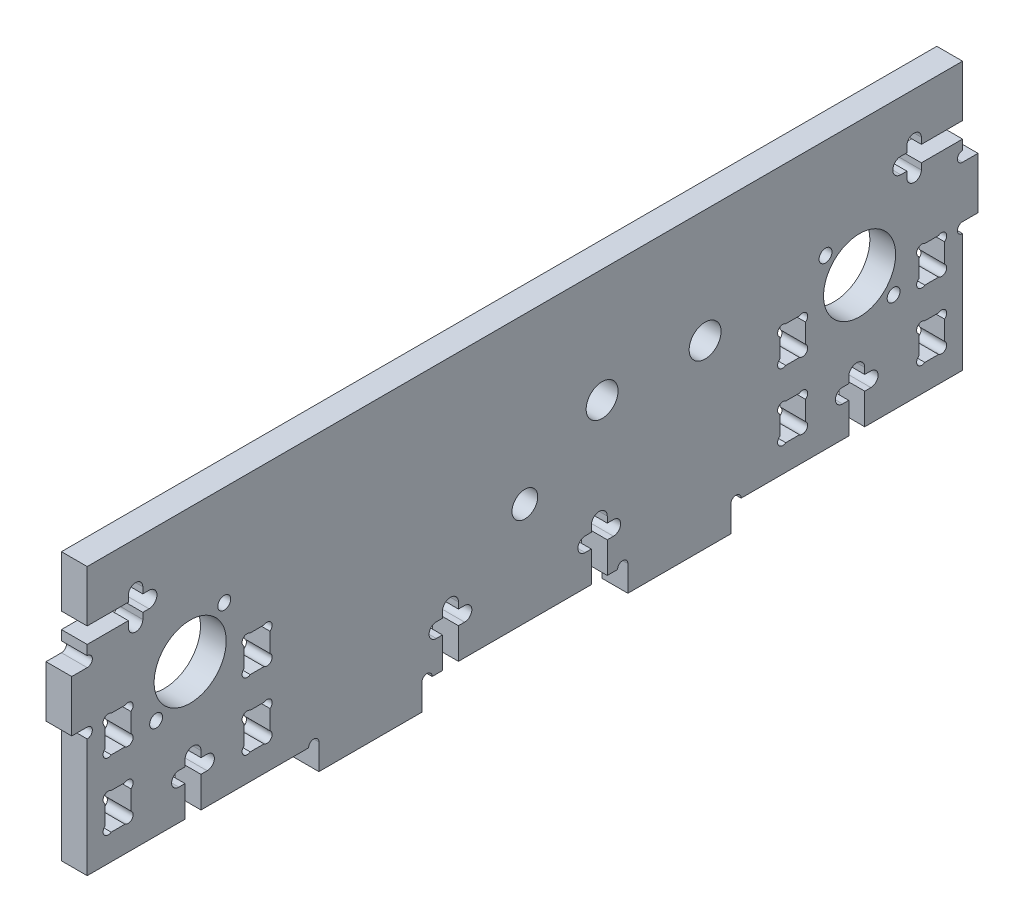
SolidWorks part; units mm, degrees
ref_plane "정면" through (0, 0, 0) normal (0, 0, 1) x (1, 0, 0)
ref_plane "윗면" through (0, 0, 0) normal (0, 1, 0) x (1, 0, 0)
ref_plane "우측면" through (0, 0, 0) normal (1, 0, 0) x (0, 0, -1)
sketch "스케치1" plane through (0, 0, 0) normal (1, 0, 0) x (0, 0, -1)
  line L1 (0, 0) -> (170, 0)
  line L2 (0, 0) -> (0, 52)
  line L3 (0, 52) -> (170, 52)
  line L4 (170, 0) -> (170, 52)
  dimension "D1" = 170
  dimension "D2" = 52
extrude "보스-돌출1" add sketch "스케치1" along normal blind 5
sketch "스케치2" plane through (5, 0, 0) normal (1, 0, 0) x (0, 0, -1)
  line L0 (170, 26) -> (150, 26) construction
  line L1 (170, 0) -> (170, 52) construction
  line L2 (150, 26) -> (20, 26) construction
  line L3 (20, 26) -> (0, 26) construction
  line L4 (0, 52) -> (0, 0) construction
  circle A0 centre (150, 26) radius 7
  circle A1 centre (20, 26) radius 7
  dimension "D2" = 14
  dimension "D1" = 20
extrude "컷-돌출1" cut sketch "스케치2" against normal blind 10
sketch "스케치3" plane through (5, 0, 0) normal (1, 0, 0) x (0, 0, -1)
  line L0 (0, 0) -> (170, 0) construction
  line L1 (45, 0) -> (65, 0)
  line L2 (45, 0) -> (45, -5)
  line L3 (45, -5) -> (65, -5)
  line L4 (65, 0) -> (65, -5)
  line L5 (0, -5) -> (45, -5) construction
  line L6 (65, -5) -> (105, -5) construction
  line L7 (125, 0) -> (105, 0)
  line L8 (125, 0) -> (125, -5)
  line L9 (125, -5) -> (105, -5)
  line L10 (105, 0) -> (105, -5)
  line L11 (125, -5) -> (170, -5) construction
  line L12 (170, -5) -> (170, 0) construction
  line L13 (0, 0) -> (0, -5) construction
  line L14 (0, 0) -> (0, -5) construction
  line L15 (0, -5) -> (45, -5) construction
  dimension "D1" = 45
  dimension "D2" = 20
extrude "보스-돌출2" add sketch "스케치3" against normal blind 5
sketch "스케치6" plane through (5, 0, 0) normal (1, 0, 0) x (0, 0, -1)
  line L0 (151, 0) -> (151, 6)
  line L1 (147.9, 10) -> (151, 10) construction
  line L2 (146.7, 6) -> (146.7, 8.8) construction
  line L3 (151, 6) -> (151, 8.8) construction
  line L4 (147.9, 0) -> (151, 0)
  line L5 (146.7, 8.8) -> (147.9, 8.8)
  line L6 (147.9, 0) -> (147.9, 6)
  line L7 (152.2, 8.8) -> (152.2, 6) construction
  line L8 (147.9, 6) -> (146.7, 6)
  line L9 (147.9, 8.8) -> (147.9, 6) construction
  line L10 (151, 8.8) -> (151, 10)
  line L11 (147.9, 6) -> (151, 6) construction
  line L12 (147.9, 8.8) -> (151, 8.8) construction
  line L13 (151, 8.8) -> (152.2, 8.8)
  line L14 (147.9, 8.8) -> (147.9, 10)
  line L15 (149.45, 10) -> (149.45, 12.1831) construction
  line L16 (152.2, 6) -> (151, 6)
  line L18 (65, 0) -> (105, 0) construction
  line L19 (101, 0) -> (101, 6)
  line L20 (97.9, 10) -> (101, 10) construction
  line L21 (96.7, 6) -> (96.7, 8.8) construction
  line L22 (101, 6) -> (101, 8.8) construction
  line L23 (97.9, 0) -> (101, 0)
  line L24 (96.7, 8.8) -> (97.9, 8.8)
  line L25 (97.9, 0) -> (97.9, 6)
  line L26 (102.2, 8.8) -> (102.2, 6) construction
  line L27 (97.9, 6) -> (96.7, 6)
  line L28 (97.9, 8.8) -> (97.9, 6) construction
  line L29 (101, 8.8) -> (101, 10)
  line L30 (97.9, 6) -> (101, 6) construction
  line L31 (97.9, 8.8) -> (101, 8.8) construction
  line L32 (101, 8.8) -> (102.2, 8.8)
  line L33 (97.9, 8.8) -> (97.9, 10)
  line L34 (99.45, 10) -> (99.45, 12.1831) construction
  line L35 (102.2, 6) -> (101, 6)
  line L37 (105, 0) -> (105, -5) construction
  line L71 (85, 52) -> (85, 0) construction
  line L72 (170, 52) -> (0, 52) construction
  line L89 (70.55, 10) -> (70.55, 12.1831) construction
  line L90 (72.1, 8.8) -> (69, 8.8) construction
  line L91 (72.1, 6) -> (69, 6) construction
  line L92 (72.1, 8.8) -> (72.1, 6) construction
  line L93 (67.8, 8.8) -> (67.8, 6) construction
  line L94 (69, 6) -> (69, 8.8) construction
  line L95 (73.3, 6) -> (73.3, 8.8) construction
  line L96 (72.1, 10) -> (69, 10) construction
  line L97 (20.55, 10) -> (20.55, 12.1831) construction
  line L98 (22.1, 8.8) -> (19, 8.8) construction
  line L99 (22.1, 6) -> (19, 6) construction
  line L100 (22.1, 8.8) -> (22.1, 6) construction
  line L101 (17.8, 8.8) -> (17.8, 6) construction
  line L102 (19, 6) -> (19, 8.8) construction
  line L103 (23.3, 6) -> (23.3, 8.8) construction
  line L104 (22.1, 10) -> (19, 10) construction
  line L123 (67.8, 6) -> (69, 6)
  line L124 (72.1, 8.8) -> (72.1, 10)
  line L125 (69, 8.8) -> (67.8, 8.8)
  line L126 (69, 8.8) -> (69, 10)
  line L127 (72.1, 6) -> (73.3, 6)
  line L128 (72.1, 0) -> (72.1, 6)
  line L129 (73.3, 8.8) -> (72.1, 8.8)
  line L130 (72.1, 0) -> (69, 0)
  line L131 (69, 0) -> (69, 6)
  line L132 (17.8, 6) -> (19, 6)
  line L133 (22.1, 8.8) -> (22.1, 10)
  line L134 (19, 8.8) -> (17.8, 8.8)
  line L135 (19, 8.8) -> (19, 10)
  line L136 (22.1, 6) -> (23.3, 6)
  line L137 (22.1, 0) -> (22.1, 6)
  line L138 (23.3, 8.8) -> (22.1, 8.8)
  line L139 (22.1, 0) -> (19, 0)
  line L140 (19, 0) -> (19, 6)
  arc A0 (151, 10) -> (147.9, 10) centre (149.45, 10) ccw
  arc A1 (146.7, 8.8) -> (146.7, 6) centre (146.7, 7.4) ccw
  arc A2 (152.2, 6) -> (152.2, 8.8) centre (152.2, 7.4) ccw
  arc A3 (101, 10) -> (97.9, 10) centre (99.45, 10) ccw
  arc A4 (96.7, 8.8) -> (96.7, 6) centre (96.7, 7.4) ccw
  arc A5 (102.2, 6) -> (102.2, 8.8) centre (102.2, 7.4) ccw
  arc A18 (67.8, 6) -> (67.8, 8.8) centre (67.8, 7.4) cw
  arc A19 (73.3, 8.8) -> (73.3, 6) centre (73.3, 7.4) cw
  arc A20 (69, 10) -> (72.1, 10) centre (70.55, 10) cw
  arc A21 (17.8, 6) -> (17.8, 8.8) centre (17.8, 7.4) cw
  arc A22 (23.3, 8.8) -> (23.3, 6) centre (23.3, 7.4) cw
  arc A23 (19, 10) -> (22.1, 10) centre (20.55, 10) cw
  dimension "D1" = 3.1
  dimension "D2" = 4
  dimension "D3" = 5.5
  dimension "D4" = 2.8
  dimension "D7" = 3.1
  dimension "D9" = 5.5
  dimension "D10" = 2.8
  dimension "D12" = 50
extrude "컷-돌출2" cut sketch "스케치6" against normal blind 10
sketch "스케치8" plane through (5, 0, 0) normal (1, 0, 0) x (0, 0, -1)
  line L0 (170, 0) -> (170, 52) construction
  line L1 (170, 35) -> (173, 35)
  line L2 (170, 35) -> (170, 25)
  line L3 (170, 25) -> (173, 25)
  line L4 (173, 35) -> (173, 25)
  line L5 (173, 52) -> (173, 35) construction
  line L8 (85, 0) -> (85, 52) construction
  line L9 (72.1, 0) -> (97.9, 0) construction
  line L10 (170, 52) -> (0, 52) construction
  line L11 (-3, 35) -> (-3, 25)
  line L12 (0, 25) -> (-3, 25)
  line L13 (0, 35) -> (0, 25)
  line L14 (0, 35) -> (-3, 35)
  line L15 (151, 0) -> (170, 0) construction
  dimension "D1" = 25
  dimension "D2" = 10
extrude "보스-돌출3" add sketch "스케치8" against normal blind 5
sketch "스케치7" plane through (5, 0, 0) normal (1, 0, 0) x (0, 0, -1)
  line L0 (65, 0) -> (69, 0) construction
  line L1 (22.1, 0) -> (45, 0) construction
  line L2 (101, 0) -> (105, 0) construction
  line L3 (125, 0) -> (147.9, 0) construction
  line L4 (170, 35) -> (170, 52) construction
  line L5 (170, 0) -> (170, 25) construction
  line L6 (0, 52) -> (0, 35) construction
  line L7 (0, 25) -> (0, 0) construction
  circle A0 centre (66, 0) radius 1
  circle A1 centre (44, 0) radius 1
  circle A2 centre (104, 0) radius 1
  circle A3 centre (126, 0) radius 1
  circle A4 centre (170, 36) radius 1
  circle A5 centre (170, 24) radius 1
  circle A6 centre (0, 36) radius 1
  circle A7 centre (0, 24) radius 1
  dimension "D1" = 2
extrude "컷-돌출3" cut sketch "스케치7" against normal blind 10
sketch "스케치10" plane through (0, 0, 0) normal (-1, 0, 0) x (0, 0, 1)
  line L0 (-166.5, 25) -> (-161.5, 18) construction
  line L1 (-166.5, 18) -> (-161.5, 18)
  line L2 (-166.5, 18) -> (-166.5, 25)
  line L3 (-166.5, 25) -> (-161.5, 25)
  line L4 (-161.5, 18) -> (-161.5, 25)
  line L5 (-161.5, 25) -> (-166.5, 18) construction
  line L6 (-85, 52) -> (-85, 0) construction
  line L7 (-139.5, 18) -> (-134.5, 18)
  line L8 (-139.5, 18) -> (-139.5, 25)
  line L9 (-139.5, 25) -> (-134.5, 25)
  line L10 (-134.5, 18) -> (-134.5, 25)
  line L11 (-166.5, 5) -> (-161.5, 5)
  line L12 (-166.5, 5) -> (-166.5, 12)
  line L13 (-166.5, 12) -> (-161.5, 12)
  line L14 (-161.5, 5) -> (-161.5, 12)
  line L15 (-139.5, 12) -> (-134.5, 12)
  line L16 (-139.5, 12) -> (-139.5, 5)
  line L17 (-139.5, 5) -> (-134.5, 5)
  line L18 (-134.5, 12) -> (-134.5, 5)
  line L19 (-170, 52) -> (0, 52) construction
  line L20 (-72.1, 0) -> (-97.9, 0) construction
  line L21 (-8.5, 25) -> (-3.5, 18) construction
  line L22 (-3.5, 25) -> (-8.5, 18) construction
  line L23 (-35.5, 12) -> (-35.5, 5)
  line L24 (-30.5, 5) -> (-35.5, 5)
  line L25 (-30.5, 12) -> (-30.5, 5)
  line L26 (-30.5, 12) -> (-35.5, 12)
  line L27 (-8.5, 5) -> (-8.5, 12)
  line L28 (-3.5, 12) -> (-8.5, 12)
  line L29 (-3.5, 5) -> (-3.5, 12)
  line L30 (-3.5, 5) -> (-8.5, 5)
  line L31 (-35.5, 18) -> (-35.5, 25)
  line L32 (-30.5, 25) -> (-35.5, 25)
  line L33 (-30.5, 18) -> (-30.5, 25)
  line L34 (-30.5, 18) -> (-35.5, 18)
  line L35 (-8.5, 18) -> (-8.5, 25)
  line L36 (-3.5, 25) -> (-8.5, 25)
  line L37 (-3.5, 18) -> (-3.5, 25)
  line L38 (-3.5, 18) -> (-8.5, 18)
extrude "컷-돌출4" cut sketch "스케치10" against normal blind 10
sketch "스케치11" plane through (5, 0, 0) normal (1, 0, 0) x (0, 0, -1)
  line L0 (85, 52) -> (85, 0) construction
  line L1 (170, 52) -> (0, 52) construction
  line L2 (72.1, 0) -> (97.9, 0) construction
  line L3 (161.5, 25) -> (166.5, 18) construction
  line L4 (166.5, 25) -> (161.5, 18) construction
  line L5 (139.5, 18) -> (161.5, 18) construction
  line L6 (161.5, 18) -> (161.5, 12) construction
  line L7 (161.5, 12) -> (139.5, 12) construction
  line L8 (139.5, 12) -> (139.5, 18) construction
  line L9 (150.5, 18) -> (150.5, 12) construction
  line L10 (139.5, 15) -> (161.5, 15) construction
  line L11 (134.5, 25) -> (139.5, 18) construction
  line L12 (139.5, 25) -> (134.5, 18) construction
  line L13 (139.5, 5) -> (134.5, 12) construction
  line L14 (134.5, 5) -> (139.5, 12) construction
  line L15 (166.5, 5) -> (161.5, 12) construction
  line L16 (161.5, 5) -> (166.5, 12) construction
  line L17 (8.5, 5) -> (3.5, 12) construction
  line L18 (3.5, 5) -> (8.5, 12) construction
  line L19 (35.5, 5) -> (30.5, 12) construction
  line L20 (30.5, 5) -> (35.5, 12) construction
  line L21 (30.5, 25) -> (35.5, 18) construction
  line L22 (35.5, 25) -> (30.5, 18) construction
  line L23 (30.5, 15) -> (8.5, 15) construction
  line L24 (19.5, 18) -> (19.5, 12) construction
  line L25 (30.5, 12) -> (30.5, 18) construction
  line L26 (8.5, 12) -> (30.5, 12) construction
  line L27 (8.5, 18) -> (8.5, 12) construction
  line L28 (30.5, 18) -> (8.5, 18) construction
  line L29 (3.5, 25) -> (8.5, 18) construction
  line L30 (8.5, 25) -> (3.5, 18) construction
  circle A0 centre (165.9188, 24.1863) radius 1
  circle A1 centre (162.0812, 24.1863) radius 1
  circle A2 centre (165.9188, 18.8137) radius 1
  circle A3 centre (162.0812, 18.8137) radius 1
  circle A4 centre (138.9188, 18.8137) radius 1
  circle A5 centre (135.0812, 18.8137) radius 1
  circle A6 centre (138.9188, 24.1863) radius 1
  circle A7 centre (135.0812, 24.1863) radius 1
  circle A8 centre (135.0812, 5.8137) radius 1
  circle A9 centre (138.9188, 5.8137) radius 1
  circle A10 centre (135.0812, 11.1863) radius 1
  circle A11 centre (138.9188, 11.1863) radius 1
  circle A12 centre (162.0812, 11.1863) radius 1
  circle A13 centre (165.9188, 11.1863) radius 1
  circle A14 centre (162.0812, 5.8137) radius 1
  circle A15 centre (165.9188, 5.8137) radius 1
  circle A16 centre (4.0812, 5.8137) radius 1
  circle A17 centre (7.9188, 5.8137) radius 1
  circle A18 centre (4.0812, 11.1863) radius 1
  circle A19 centre (7.9188, 11.1863) radius 1
  circle A20 centre (31.0812, 11.1863) radius 1
  circle A21 centre (34.9188, 11.1863) radius 1
  circle A22 centre (31.0812, 5.8137) radius 1
  circle A23 centre (34.9188, 5.8137) radius 1
  circle A24 centre (34.9188, 24.1863) radius 1
  circle A25 centre (31.0812, 24.1863) radius 1
  circle A26 centre (34.9188, 18.8137) radius 1
  circle A27 centre (31.0812, 18.8137) radius 1
  circle A28 centre (7.9188, 18.8137) radius 1
  circle A29 centre (4.0812, 18.8137) radius 1
  circle A30 centre (7.9188, 24.1863) radius 1
  circle A31 centre (4.0812, 24.1863) radius 1
  dimension "D1" = 2
extrude "컷-돌출5" cut sketch "스케치11" against normal blind 10
sketch "스케치12" plane through (5, 0, 0) normal (1, 0, 0) x (0, 0, -1)
  line L0 (170, 42) -> (162, 42)
  line L1 (158, 38.9) -> (158, 42) construction
  line L2 (162, 37.7) -> (159.2, 37.7) construction
  line L3 (162, 42) -> (159.2, 42) construction
  line L4 (170, 38.9) -> (170, 42)
  line L5 (159.2, 37.7) -> (159.2, 38.9)
  line L6 (170, 38.9) -> (162, 38.9)
  line L7 (159.2, 43.2) -> (162, 43.2) construction
  line L8 (162, 38.9) -> (162, 37.7)
  line L9 (159.2, 38.9) -> (162, 38.9) construction
  line L10 (159.2, 42) -> (158, 42)
  line L11 (162, 38.9) -> (162, 42) construction
  line L12 (159.2, 38.9) -> (159.2, 42) construction
  line L13 (159.2, 42) -> (159.2, 43.2)
  line L14 (159.2, 38.9) -> (158, 38.9)
  line L15 (158, 40.45) -> (156.45, 40.45) construction
  line L16 (162, 43.2) -> (162, 42)
  line L17 (160.6, 37.7) -> (160.6, 38.9) construction
  line L18 (160.6, 43.2) -> (160.6, 42) construction
  line L19 (159.2, 40.45) -> (158, 40.45) construction
  line L20 (160.6, 43.2) -> (160.6, 44.6) construction
  line L21 (160.6, 37.7) -> (160.6, 36.3) construction
  line L22 (170, 37) -> (170, 52) construction
  line L23 (170, 52) -> (0, 52) construction
  line L24 (85, 52) -> (85, 0) construction
  line L25 (72.1, 0) -> (97.9, 0) construction
  line L26 (9.4, 37.7) -> (9.4, 36.3) construction
  line L27 (9.4, 43.2) -> (9.4, 44.6) construction
  line L28 (10.8, 40.45) -> (12, 40.45) construction
  line L29 (9.4, 43.2) -> (9.4, 42) construction
  line L30 (9.4, 37.7) -> (9.4, 38.9) construction
  line L31 (12, 40.45) -> (13.55, 40.45) construction
  line L32 (10.8, 38.9) -> (10.8, 42) construction
  line L33 (8, 38.9) -> (8, 42) construction
  line L34 (10.8, 38.9) -> (8, 38.9) construction
  line L35 (10.8, 43.2) -> (8, 43.2) construction
  line L36 (8, 42) -> (10.8, 42) construction
  line L37 (8, 37.7) -> (10.8, 37.7) construction
  line L38 (12, 38.9) -> (12, 42) construction
  line L39 (8, 43.2) -> (8, 42)
  line L40 (10.8, 38.9) -> (12, 38.9)
  line L41 (10.8, 42) -> (10.8, 43.2)
  line L42 (10.8, 42) -> (12, 42)
  line L43 (8, 38.9) -> (8, 37.7)
  line L44 (0, 38.9) -> (8, 38.9)
  line L45 (10.8, 37.7) -> (10.8, 38.9)
  line L46 (0, 38.9) -> (0, 42)
  line L47 (0, 42) -> (8, 42)
  arc A0 (158, 42) -> (158, 38.9) centre (158, 40.45) ccw
  arc A1 (159.2, 37.7) -> (162, 37.7) centre (160.6, 37.7) ccw
  arc A2 (162, 43.2) -> (159.2, 43.2) centre (160.6, 43.2) ccw
  arc A3 (8, 43.2) -> (10.8, 43.2) centre (9.4, 43.2) cw
  arc A4 (10.8, 37.7) -> (8, 37.7) centre (9.4, 37.7) cw
  arc A5 (12, 42) -> (12, 38.9) centre (12, 40.45) cw
  dimension "D1" = 3.1
  dimension "D2" = 5.5
  dimension "D3" = 2.8
  dimension "D4" = 1.2
  dimension "D5" = 10
  dimension "D6" = 3.1
  dimension "D7" = 8
extrude "컷-돌출6" cut sketch "스케치12" against normal blind 10
sketch "스케치13" plane through (5, 0, 0) normal (1, 0, 0) x (0, 0, -1)
  line L0 (120, 30) -> (100, 30) construction
  line L1 (127, 0) -> (147.9, 0) construction
  line L2 (170, 37) -> (170, 38.9) construction
  line L3 (72.1, 0) -> (97.9, 0) construction
  circle A0 centre (100, 30) radius 3.1
  circle A1 centre (120, 30) radius 3.1
  circle A2 centre (85, 20) radius 2.5
  dimension "D1" = 6.2
  dimension "D5" = 20
  dimension "D6" = 5
  dimension "D2" = 20
  dimension "D3" = 30
  dimension "D4" = 50
extrude "컷-돌출7" cut sketch "스케치13" against normal blind 10
sketch "스케치14" plane through (5, 0, 0) normal (1, 0, 0) x (0, 0, -1)
  line L0 (150, 26) -> (155.6569, 20.3431) construction
  line L1 (155.6569, 20.3431) -> (156.6114, 19.3886) construction
  line L2 (150, 26) -> (150, 14.9084) construction
  line L3 (150, 26) -> (155.6569, 31.6569) construction
  line L4 (85, 52) -> (85, 0) construction
  line L5 (170, 52) -> (0, 52) construction
  line L6 (72.1, 0) -> (97.9, 0) construction
  circle A1 centre (150, 26) radius 8 construction
  circle A2 centre (156.6114, 19.3886) radius 1.25
  circle A3 centre (143.3886, 32.6114) radius 1.25
  circle A4 centre (13.3886, 19.3886) radius 1.25
  circle A5 centre (26.6114, 32.6114) radius 1.25
  dimension "D1" = 2.5
  dimension "D2" = 1.35
  dimension "D3" = 45
extrude "컷-돌출8" cut sketch "스케치14" against normal blind 10
